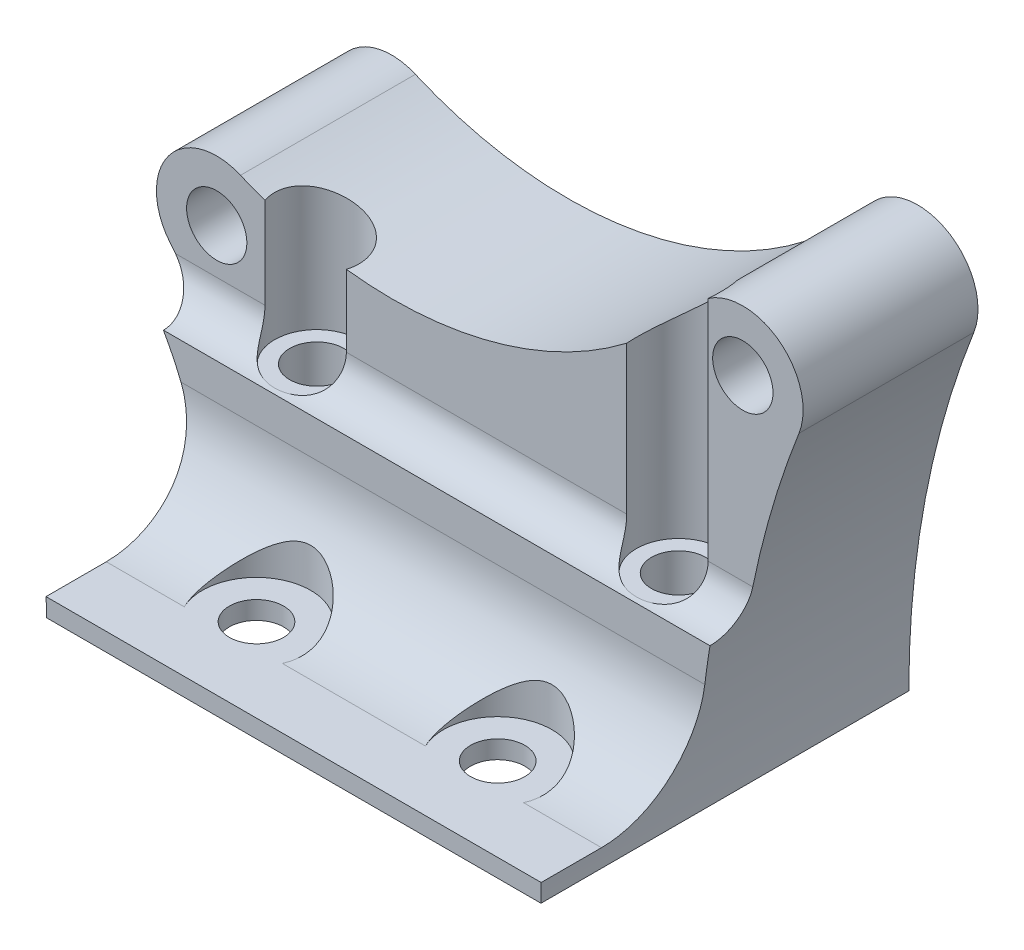
SolidWorks part; units mm, degrees
ref_plane "Płaszczyzna przednia" through (0, 0, 0) normal (0, 0, 1) x (1, 0, 0)
ref_plane "Płaszczyzna górna" through (0, 0, 0) normal (0, 1, 0) x (1, 0, 0)
ref_plane "Płaszczyzna prawa" through (0, 0, 0) normal (1, 0, 0) x (0, 0, -1)
sketch "Szkic1" plane through (0, 0, 0) normal (0, 0, 1) x (1, 0, 0)
  line L0 (-1.47, -60.54) -> (-83.47, -60.54)
  line L1 (-42.47, -60.54) -> (-42.47, -34.6311) construction
  circle A0 centre (-87.247, -22.09) radius 5
  circle A1 centre (0, 0) radius 5
  arc A2 (9.307, -3.6579) -> (-7.8435, 6.2031) centre (0, 0) ccw
  arc A3 (-83.3004, -12.9017) -> (-94.9714, -28.4408) centre (-87.247, -22.09) ccw
  arc A4 (-1.47, -60.54) -> (9.307, -3.6579) centre (154.0338, -60.54) cw
  arc A6 (-83.47, -60.54) -> (-94.9714, -28.4408) centre (-134.0133, -60.54) ccw
  arc A8 (-83.3004, -12.9017) -> (-7.8435, 6.2031) centre (-58.0422, 45.9032) ccw
  dimension "D1" = 10
  dimension "D2" = 10
  dimension "D7" = 20
  dimension "D8" = 20
  dimension "D9" = 155.5038
  dimension "D10" = 64
  dimension "D3" = 90
  dimension "D4" = 82
  dimension "D5" = 60.54
  dimension "D6" = 38.45
extrude "Dodanie-wyciągnięcie1" add sketch "Szkic1" along normal blind 27.7
sketch "Szkic3" plane through (0, 0, 0) normal (1, 0, 0) x (0, 0, -1)
  line L0 (0, -60.54) -> (0, -41.54)
  line L1 (0, -60.54) -> (20.3, -60.54)
  line L2 (-27.7, -60.54) -> (0, -60.54) construction
  line L7 (0, -27.09) -> (0, -17.09) construction
  line L8 (16, -57.54) -> (20.3, -57.54)
  line L9 (20.3, -57.54) -> (20.3, -60.54)
  line L10 (-27.7, -3.6579) -> (-27.7, -60.54) construction
  arc A0 (16, -57.54) -> (0, -41.54) centre (16, -41.54) cw
  dimension "D1" = 48
  dimension "D2" = 3
  dimension "D3" = 19
extrude "Dodanie-wyciągnięcie2" add sketch "Szkic3" against normal up to surface (87.1771 mm away) up to face at (-87.8264, -43.9908, 13.85)
sketch "Szkic4" plane through (0, 0, 0) normal (0, 0, 1) x (1, 0, 0)
  line L0 (-1.47, -60.54) -> (0, -60.54)
  line L1 (0, -60.54) -> (0, -41.54)
  line L2 (0, -41.54) -> (-0.3049, -41.54)
  arc A0 (-1.47, -60.54) -> (-0.3049, -41.54) centre (154.0338, -60.54) cw
  arc A1 (-0.3049, -41.54) -> (-1.47, -60.54) centre (154.0338, -60.54) ccw construction
extrude "Wytnij-wyciągnięcie1" cut sketch "Szkic4" against normal up to surface (20.3 mm away) up to face at (-41.7517, -59.0398, -20.3)
hole_wizard "Pogłębienie walcowe pod M8 Wkręt z łbem sześciokątnym z gniazdem1" positions "Szkic7" profile "Szkic9" counterbore size "M8" standard "ISO" end condition through all
sketch "Szkic7" plane through (0, 0, 0) normal (0, 1, 0) x (1, 0, 0)
  line L4 (-17.3275, -13.85) -> (-81.7271, -13.85) construction
  line L7 (-7.8435, 0) -> (-83.3004, 0) construction
  line L8 (-83.3004, -27.7) -> (-7.8435, -27.7) construction
  line L19 (-42.5001, -52.7037) -> (-42.5001, 17.1743) construction
  line L21 (-83.5591, 16) -> (-83.5591, 20.3) construction
  line L22 (-1.441, 20.3) -> (-1.441, 16) construction
  point P0 (-62.5001, -13.85)
  point P2 (-22.5001, -13.85)
  dimension "D1" = 40
sketch "Szkic9" plane through (-62.5001, 0, 13.85) normal (1, 0, 0) x (0, 0, 1)
  line L0 (0, 0) -> (0, 60.54)
  line L1 (0, 60.54) -> (4.5, 60.54)
  line L3 (4.5, 60.54) -> (4.5, 20.3)
  line L4 (4.5, 20.3) -> (9.0055, 20.3)
  line L5 (9.0055, 20.3) -> (9.0055, 0)
  line L7 (9.0055, 0) -> (0, 0)
  line L11 (0, -6.35) -> (0, 107.95) construction
  dimension "Średnica otworu na wylot" = 9
  dimension "Głębokość otworu na wylot" = 60.54
  dimension "Średnica pogłębienia walcowego" = 18.011
  dimension "Głębokość pogłębienia walcowego" = 20.3
hole_wizard "Pogłębienie walcowe pod M8 Wkręt z łbem sześciokątnym z gniazdem3" positions "Szkic10" profile "Szkic11" counterbore size "M8" standard "ISO" end condition through all
sketch "Szkic10" plane through (0, 0, 0) normal (0, 1, 0) x (1, 0, 0)
  line L0 (-25.0973, 10.15) -> (-137.2488, 10.15) construction
  line L3 (-83.5591, 20.3) -> (-1.441, 20.3) construction
  line L4 (-87.1771, 0) -> (-0.3049, 0) construction
  line L5 (-42.5001, -25.0215) -> (-42.5001, 41.234) construction
  line L7 (-1.441, 20.3) -> (-1.441, 16) construction
  line L8 (-83.5591, 16) -> (-83.5591, 20.3) construction
  point P0 (-72.5001, 10.15)
  point P2 (-12.5001, 10.15)
  dimension "D1" = 60
sketch "Szkic11" plane through (-72.5001, 0, -10.15) normal (1, 0, 0) x (0, 0, 1)
  line L0 (0, 0) -> (0, 60.54)
  line L1 (0, 60.54) -> (4.5, 60.54)
  line L3 (4.5, 60.54) -> (4.5, 57.54)
  line L4 (4.5, 57.54) -> (9.0055, 57.54)
  line L5 (9.0055, 57.54) -> (9.0055, 0)
  line L7 (9.0055, 0) -> (0, 0)
  line L11 (0, -6.35) -> (0, 107.95) construction
  dimension "Średnica otworu na wylot" = 9
  dimension "Głębokość otworu na wylot" = 60.54
  dimension "Średnica pogłębienia walcowego" = 18.011
  dimension "Głębokość pogłębienia walcowego" = 57.54
extrude "Boss-Extrude1" add sketch "Szkic1<3>" against normal blind 29 from offset 4.3 offset against normal yes
sketch "Szkic1<3>" plane through (0, 0, 0) normal (0, 0, 1) x (1, 0, 0) same geometry as "Szkic1"
sketch "Sketch2" plane through (0, 0, 0) normal (1, 0, 0) x (0, 0, -1)
  line L0 (4.3, 30.0355) -> (4.3, -57.54)
  line L1 (4.3, 30.0355) -> (-36.6661, 30.0355)
  line L2 (-36.6661, 30.0355) -> (-36.6661, -57.54)
  line L3 (-36.6661, -57.54) -> (4.3, -57.54)
  line L4 (-27.7, -60.54) -> (33.3, -60.54) construction
  line L5 (4.3, -3.6579) -> (4.3, -52.4538) construction
  dimension "D1" = 3
extrude "Cut-Extrude2" cut sketch "Sketch2" against normal blind 159.1177 and the other way blind 108
sketch "Sketch9" plane through (0, 0, -4.3) normal (0, 0, 1) x (1, 0, 0)
  line L1 (-83.5591, -57.54) -> (-1.441, -57.54)
  line L3 (-83.5591, -57.54) -> (-1.441, -57.54)
  arc A5 (-83.5591, -57.54) -> (-94.9714, -28.4408) centre (-134.0133, -60.54) ccw
  arc A6 (9.307, -3.6579) -> (-1.441, -57.54) centre (154.0338, -60.54) ccw
  arc A7 (9.307, -3.6579) -> (-7.8435, 6.2031) centre (0, 0) ccw
  arc A8 (-83.3004, -12.9017) -> (-7.8435, 6.2031) centre (-58.0422, 45.9032) ccw
  arc A9 (-83.3004, -12.9017) -> (-94.9714, -28.4408) centre (-87.247, -22.09) ccw
  arc A10 (-83.5591, -57.54) -> (-94.9714, -28.4408) centre (-134.0133, -60.54) ccw
  arc A11 (9.307, -3.6579) -> (-1.441, -57.54) centre (154.0338, -60.54) ccw
  arc A12 (9.307, -3.6579) -> (-7.8435, 6.2031) centre (0, 0) ccw
  arc A13 (-83.3004, -12.9017) -> (-7.8435, 6.2031) centre (-58.0422, 45.9032) ccw
  arc A14 (-83.3004, -12.9017) -> (-94.9714, -28.4408) centre (-87.247, -22.09) ccw
  dimension "D1" = 0
extrude "Boss-Extrude3" add sketch "Sketch9" along normal blind 6
sketch "Sketch4" plane through (0, -60.54, 0) normal (0, -1, 0) x (-1, 0, 0)
  line L0 (62.5001, -13.85) -> (22.5001, -13.85) construction
  line L1 (42.5001, -13.85) -> (42.5001, 37.3653) construction
  circle A0 centre (12.5001, 6.15) radius 4.5
  circle A1 centre (72.5001, 6.15) radius 4.5
  circle A3 centre (22.5001, -13.85) radius 4.5 construction
  dimension "D1" = 60
  dimension "D5" = 9
  dimension "D2" = 20
  dimension "D3" = 30
sketch "Sketch10" plane through (0, -57.54, 0) normal (0, 1, 0) x (1, 0, 0)
  line L0 (-83.5591, -27.7) -> (-1.441, -27.7) construction
  line L1 (-103.5591, 4.3) -> (18.559, 4.3)
  line L2 (-103.5591, 4.3) -> (-103.5591, -27.7)
  line L3 (-103.5591, -27.7) -> (18.559, -27.7)
  line L4 (18.559, 4.3) -> (18.559, -27.7)
  line L5 (-1.441, -27.7) -> (-1.441, -1.7) construction
  line L6 (-83.5591, -1.7) -> (-83.5591, -27.7) construction
  line L7 (-7.8435, -1.7) -> (10, -1.7) construction
  dimension "D1" = 20
  dimension "D2" = 20
  dimension "D3" = 6
fillet "Fillet4" radius 16 1 edges at (-42.5001, -57.54, 1.7)
extrude "Wytnij-wyciągnięcie2" cut sketch "Sketch10" along normal blind 59 and the other way blind 1 from offset 23
fillet "Zaokrąglenie7" radius 6 1 edges at (-44.7665, -35.54, -4.3)
extrude "Wytnij-wyciągnięcie3" cut sketch "Sketch4" against normal through all
sketch "Szkic14" plane through (0, -60.54, 0) normal (0, -1, 0) x (1, 0, 0)
  circle A0 centre (-72.5001, -6.15) radius 7
  circle A1 centre (-12.5001, -6.15) radius 7
  dimension "D1" = 14
  dimension "D2" = 14
extrude "Wytnij-wyciągnięcie4" cut sketch "Szkic14" against normal through all from offset 25 offset against normal yes
sketch "Szkic15" plane through (0, -57.54, 0) normal (0, 1, 0) x (1, 0, 0)
  circle A0 centre (-62.5001, -13.85) radius 9
  circle A1 centre (-22.5001, -13.85) radius 9
  dimension "D1" = 18
  dimension "D2" = 18
extrude "Wytnij-wyciągnięcie5" cut sketch "Szkic15" along normal through all
